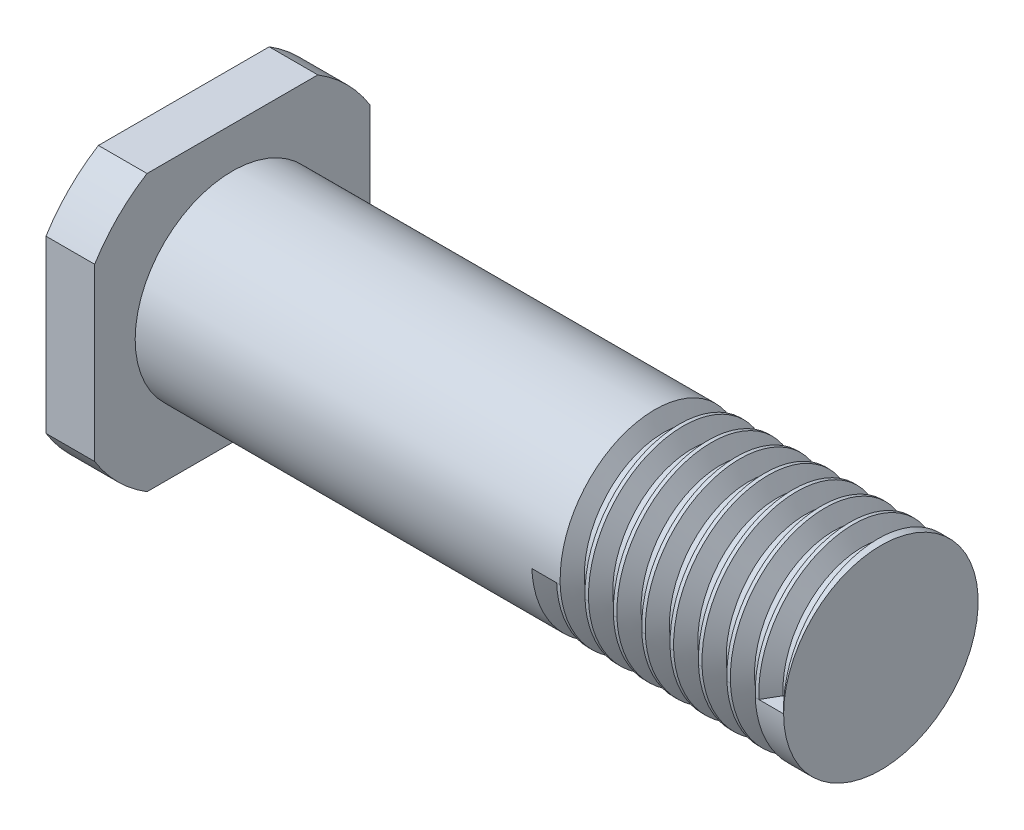
SolidWorks part; units mm, degrees
material "A3钢"
ref_plane "前视基准面" through (0, 0, 0) normal (0, 0, 1) x (1, 0, 0)
ref_plane "上视基准面" through (0, 0, 0) normal (0, 1, 0) x (1, 0, 0)
ref_plane "右视基准面" through (0, 0, 0) normal (1, 0, 0) x (0, 0, -1)
sketch "草图1" plane through (0, 0, 0) normal (0, 0, 1) x (1, 0, 0)
  line L0 (0, 0) -> (0, 10)
  line L1 (0, 10) -> (3, 10)
  line L2 (3, 10) -> (3, 6)
  line L3 (3, 6) -> (43, 6)
  line L4 (43, 6) -> (43, 0)
  line L5 (43, 0) -> (0, 0)
  line L6 (-4.2727, 0) -> (32.2727, 0) construction
  dimension "D1" = 20
  dimension "D2" = 43
  dimension "D3" = 3
  dimension "D4" = 12
revolve "旋转1" add sketch "草图1" angle 360 about L6
sketch "草图2" plane through (0, 0, 0) normal (-1, 0, 0) x (0, 0, 1)
  line L1 (-8.5, -8.5) -> (8.5, -8.5)
  line L2 (-8.5, -8.5) -> (-8.5, 8.5)
  line L3 (-8.5, 8.5) -> (8.5, 8.5)
  line L4 (8.5, -8.5) -> (8.5, 8.5)
  line L5 (-8.5, -8.5) -> (8.5, 8.5) construction
  line L6 (-8.5, 8.5) -> (8.5, -8.5) construction
  point P0 (0, 0)
  dimension "D1" = 17
  dimension "D2" = 17
extrude "切除-拉伸1" cut sketch "草图2" against normal through all flip side to cut
thread "螺纹线1" pitch 1.75 method cut profile "螺纹线轮廓1" start angle 0, offset 0, length 14, pitch 1.75, diameter 12
ref_plane "基准面1" through (43, 0, 6) normal (0, -1, 0) x (0, 0, 1)
sketch "螺纹线轮廓1" plane through (43, 0, 6) normal (0, -1, 0) x (0, 0, 1)
  line L0 (0, 0) -> (0, 1.75) construction
  line L11 (0, 0) -> (0, 1.5312)
  line L12 (0, 1.5312) -> (-0.9472, 0.9844)
  line L13 (-0.9472, 0.9844) -> (-0.9472, 0.5469)
  line L15 (-0.9472, 0.5469) -> (0, 0)
  line L17 (-0.9472, 0.7656) -> (0, 0.7656) construction
  point P2 (0, 0)
  dimension "Pitch" = 1.75
  dimension "Profile_Angle" = 60
  dimension "Profile_Land" = 0.4375
  dimension "Profile_Height" = 0.9472
